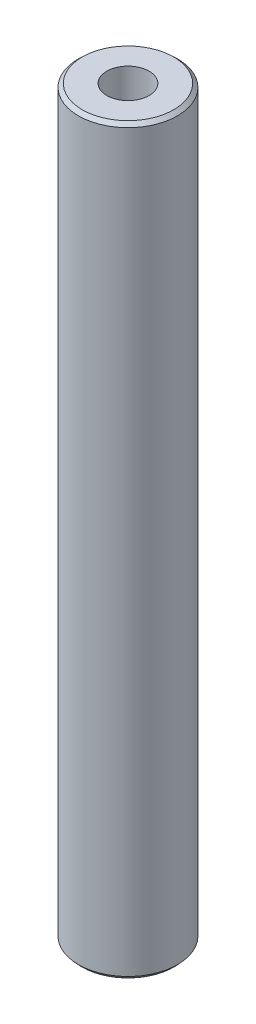
SolidWorks part; units mm, degrees
ref_plane "Front Plane" through (0, 0, 0) normal (0, 0, 1) x (1, 0, 0)
ref_plane "Top Plane" through (0, 0, 0) normal (0, 1, 0) x (1, 0, 0)
ref_plane "Right Plane" through (0, 0, 0) normal (1, 0, 0) x (0, 0, -1)
sketch "Sketch1" plane through (0, 0, 0) normal (0, 1, 0) x (1, 0, 0)
  circle A0 centre (0, 0) radius 40
  dimension "SHAFT_OD" = 80
extrude "Boss-Extrude1" add sketch "Sketch1" along normal blind 600
sketch "Sketch2" plane through (0, 0, 0) normal (0, 1, 0) x (1, 0, 0)
  circle A0 centre (0, 0) radius 17.0956
  dimension "BORE_D" = 34.1912
extrude "Cut-Extrude1" cut sketch "Sketch2" along normal through all
chamfer "Chamfer1" distance 2.7702 angle 47.516 2 edges at (0, 600, 40) (0, 0, 40) first distance on face at (0, 600, 40) first distance on face at (0, 0, 17.0956)
